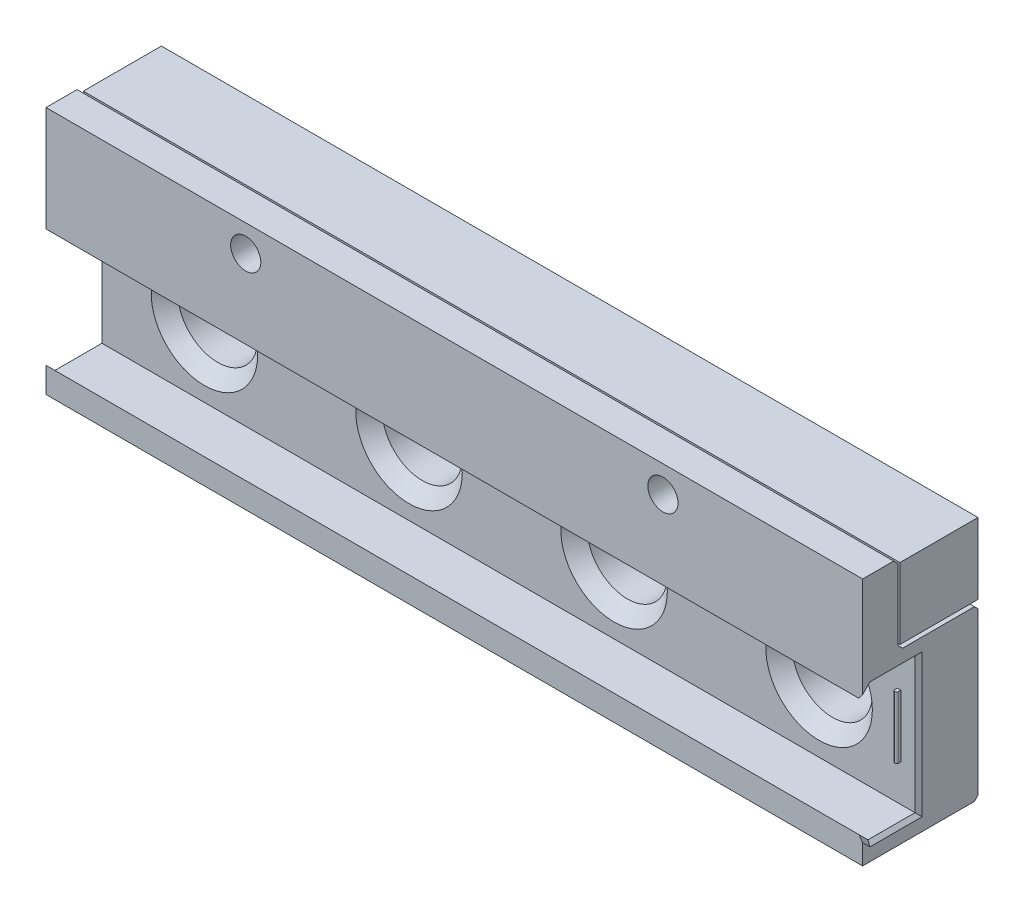
SolidWorks part; units mm, degrees
ref_plane "Front Plane" through (0, 0, 0) normal (0, 0, 1) x (1, 0, 0)
ref_plane "Top Plane" through (0, 0, 0) normal (0, 1, 0) x (1, 0, 0)
ref_plane "Right Plane" through (0, 0, 0) normal (1, 0, 0) x (0, 0, -1)
sketch "Sketch1" plane through (0, 0, 0) normal (0, 0, 1) x (1, 0, 0)
  line L1 (-61.1072, 25.5521) -> (30.8928, 25.5521)
  line L2 (-61.1072, 25.5521) -> (-61.1072, 6.5521)
  line L3 (-61.1072, 6.5521) -> (30.8928, 6.5521)
  line L4 (30.8928, 25.5521) -> (30.8928, 6.5521)
  dimension "D1" = 92
  dimension "D2" = 19
extrude "Boss-Extrude1" add sketch "Sketch1" along normal blind 13
sketch "Sketch2" plane through (0, 0, 13) normal (0, 0, 1) x (1, 0, 0)
  line L0 (-61.1072, 25.5521) -> (-61.1072, 6.5521) construction
  line L1 (-61.1072, 6.5521) -> (30.8928, 6.5521) construction
  circle A0 centre (-49.5572, 16.0521) radius 4.5
  dimension "D1" = 9
  dimension "D2" = 11.55
  dimension "D3" = 9.5
extrude "Cut-Extrude1" cut sketch "Sketch2" against normal through all
sketch "Sketch4" plane through (0, 0, 13) normal (0, 0, 1) x (1, 0, 0)
  line L0 (-61.1072, 6.5521) -> (30.8928, 6.5521) construction
  circle A0 centre (-26.5072, 16.0521) radius 4.5
  circle A1 centre (-49.5572, 16.0521) radius 4.5 construction
  dimension "D2" = 9
  dimension "D1" = 23.05
  dimension "D3" = 9.5
extrude "Cut-Extrude2" cut sketch "Sketch4" against normal through all
sketch "Sketch5" plane through (0, 0, 13) normal (0, 0, 1) x (1, 0, 0)
  line L0 (-61.1072, 6.5521) -> (30.8928, 6.5521) construction
  circle A0 centre (-3.4072, 16.0521) radius 4.5
  circle A1 centre (-26.5072, 16.0521) radius 4.5 construction
  dimension "D2" = 9
  dimension "D1" = 23.1
  dimension "D3" = 9.5
extrude "Cut-Extrude3" cut sketch "Sketch5" against normal through all
sketch "Sketch6" plane through (0, 0, 13) normal (0, 0, 1) x (1, 0, 0)
  line L0 (-61.1072, 6.5521) -> (30.8928, 6.5521) construction
  circle A0 centre (19.6928, 16.0521) radius 4.5
  circle A1 centre (-3.4072, 16.0521) radius 4.5 construction
  dimension "D3" = 9
  dimension "D1" = 23.1
  dimension "D2" = 9.5
extrude "Cut-Extrude4" cut sketch "Sketch6" against normal through all
sketch "Sketch7" plane through (0, 0, 13) normal (0, 0, 1) x (1, 0, 0)
  line L0 (-61.1072, 25.5521) -> (-61.1072, 6.5521) construction
  line L1 (-61.1072, 23.7021) -> (30.8928, 23.7021)
  line L2 (-61.1072, 23.7021) -> (-61.1072, 8.4021)
  line L3 (-61.1072, 8.4021) -> (30.8928, 8.4021)
  line L4 (30.8928, 23.7021) -> (30.8928, 8.4021)
  line L5 (30.8928, 6.5521) -> (30.8928, 25.5521) construction
  line L6 (30.8928, 25.5521) -> (-61.1072, 25.5521) construction
  line L7 (-61.1072, 6.5521) -> (30.8928, 6.5521) construction
  dimension "D1" = 1.85
  dimension "D2" = 1.85
extrude "Cut-Extrude5" cut sketch "Sketch7" against normal blind 6.3
sketch "Sketch11" plane through (0, 25.5521, 0) normal (0, 1, 0) x (1, 0, 0)
  line L0 (30.8928, -13) -> (30.8928, 0) construction
  line L1 (-61.1072, -13) -> (30.8928, -13)
  line L2 (-61.1072, -13) -> (-61.1072, -9)
  line L3 (-61.1072, -9) -> (30.8928, -9)
  line L4 (30.8928, -13) -> (30.8928, -9)
  dimension "D1" = 4
extrude "Boss-Extrude4" add sketch "Sketch11" along normal blind 9
sketch "Sketch12" plane through (0, 0, 13) normal (0, 0, 1) x (1, 0, 0)
  line L0 (-61.1072, 34.5521) -> (30.8928, 34.5521) construction
  line L1 (-61.1072, 34.5521) -> (-61.1072, 23.7021) construction
  circle A0 centre (-38.6072, 31.5521) radius 1.7
  dimension "D1" = 3.4
  dimension "D2" = 3
  dimension "D3" = 22.5
extrude "Cut-Extrude6" cut sketch "Sketch12" against normal through all
sketch "Sketch13" plane through (0, 0, 13) normal (0, 0, 1) x (1, 0, 0)
  line L0 (-61.1072, 34.5521) -> (30.8928, 34.5521) construction
  line L1 (30.8928, 23.7021) -> (30.8928, 34.5521) construction
  circle A0 centre (8.3928, 31.5521) radius 1.7
  dimension "D1" = 3.4
  dimension "D2" = 3
  dimension "D3" = 22.5
extrude "Cut-Extrude7" cut sketch "Sketch13" against normal through all
chamfer "Chamfer1" distance 0.4 angle 45 2 edges at (-15.1072, 25.5521, 0) (-15.1072, 6.5521, 0)
chamfer "Chamfer2" distance 0.5 angle 45 2 edges at (-36.9072, 31.5521, 9) (10.0928, 31.5521, 9)
chamfer "Chamfer3" distance 0.5 angle 45 1 edges at (-15.1072, 25.5521, 9)
chamfer "Chamfer4" distance 0.5 angle 45 1 edges at (-15.1072, 34.5521, 9)
sketch "Sketch14" plane through (0, 0, 0) normal (0, 0, -1) x (-1, 0, 0)
  line L1 (-30.8928, 34.0521) -> (61.1072, 34.0521)
  line L2 (-30.8928, 34.0521) -> (-30.8928, 26.0521)
  line L3 (-30.8928, 26.0521) -> (61.1072, 26.0521)
  line L4 (61.1072, 34.0521) -> (61.1072, 26.0521)
extrude "Boss-Extrude5" add sketch "Sketch14" against normal blind 8.8 separate body
chamfer "Chamfer5" distance 1.5 angle 45 4 edges at (24.1928, 16.0521, 6.7) (1.0928, 16.0521, 6.7) (-22.0072, 16.0521, 6.7) (-45.0572, 16.0521, 6.7)
sketch "Sketch19" plane through (30.8928, 0, 0) normal (1, 0, 0) x (0, 0, -1)
  line L0 (-13, 23.7021) -> (-12, 23.7021)
  line L1 (-6.7, 23.7021) -> (-13, 23.7021) construction
  line L2 (-12, 23.7021) -> (-13, 22.7021)
  line L3 (-13, 22.7021) -> (-13, 23.7021)
  line L4 (-13, 8.4021) -> (-12, 8.4021)
  line L5 (-6.7, 8.4021) -> (-13, 8.4021) construction
  line L6 (-12, 8.4021) -> (-13, 9.4021)
  line L7 (-13, 9.4021) -> (-13, 8.4021)
  dimension "D1" = 1
  dimension "D2" = 1
  dimension "D3" = 1
extrude "Boss-Extrude8" add sketch "Sketch19" against normal up to surface (92 mm away) up to face at (-61.1072, 20.695, 7.3)
sketch "Sketch20" plane through (0, 0, 6.7) normal (0, 0, 1) x (1, 0, 0)
  line L1 (28.4928, 19.5521) -> (28.8928, 19.5521)
  line L2 (28.4928, 19.5521) -> (28.4928, 12.5521)
  line L3 (28.4928, 12.5521) -> (28.8928, 12.5521)
  line L4 (28.8928, 19.5521) -> (28.8928, 12.5521)
  line L5 (30.8928, 23.7021) -> (-61.1072, 23.7021) construction
  line L6 (30.8928, 8.4021) -> (30.8928, 23.7021) construction
  dimension "D1" = 0.4
  dimension "D2" = 7
  dimension "D3" = 2
  dimension "D4" = 4.15
chamfer "Chamfer6" distance 0.4 angle 45 5 edges at (30.8928, 23.2021, 12.5) (30.8928, 23.7021, 9.35) (30.8928, 16.0521, 6.7) (30.8928, 8.4021, 9.35) (30.8928, 8.9021, 12.5)
extrude "Boss-Extrude9" add sketch "Sketch20" along normal blind 0.75
fillet "Fillet1" radius 0.5 1 edges at (28.4928, 16.0521, 7.45)
fillet "Fillet2" radius 0.2 1 edges at (28.8928, 16.0521, 7.45)
sketch "Sketch25" plane through (0, 0, 8.8) normal (0, 0, 1) x (1, 0, 0)
  line L0 (-61.1072, 26.0521) -> (-61.1072, 34.0521) construction
  line L1 (-60.1072, 33.0521) -> (29.8928, 33.0521)
  line L2 (-60.1072, 33.0521) -> (-60.1072, 27.0521)
  line L3 (-60.1072, 27.0521) -> (29.8928, 27.0521)
  line L4 (29.8928, 33.0521) -> (29.8928, 27.0521)
  line L5 (-61.1072, 34.0521) -> (30.8928, 34.0521) construction
  line L6 (30.8928, 26.0521) -> (-61.1072, 26.0521) construction
  line L7 (30.8928, 34.0521) -> (30.8928, 26.0521) construction
  dimension "D1" = 1
  dimension "D2" = 1
  dimension "D3" = 1
  dimension "D4" = 1
extrude "Cut-Extrude10" cut sketch "Sketch25" against normal blind 1
sketch "Sketch26" plane through (0, 0, 0) normal (0, 0, -1) x (-1, 0, 0)
  line L0 (-30.8928, 34.0521) -> (-30.8928, 26.0521) construction
  line L1 (-29.8928, 33.0521) -> (60.1072, 33.0521)
  line L2 (-29.8928, 33.0521) -> (-29.8928, 27.0521)
  line L3 (-29.8928, 27.0521) -> (60.1072, 27.0521)
  line L4 (60.1072, 33.0521) -> (60.1072, 27.0521)
  line L5 (61.1072, 34.0521) -> (-30.8928, 34.0521) construction
  line L6 (-30.8928, 26.0521) -> (61.1072, 26.0521) construction
  line L7 (61.1072, 26.0521) -> (61.1072, 34.0521) construction
  dimension "D1" = 1
  dimension "D2" = 1
  dimension "D3" = 1
  dimension "D4" = 1
extrude "Cut-Extrude11" cut sketch "Sketch26" against normal blind 6.9
sketch "Sketch28" plane through (0, 0, 8.8) normal (0, 0, 1) x (1, 0, 0)
  line L0 (-60.1072, 33.0521) -> (-55.906, 27.0521)
  line L1 (-60.1072, 27.0521) -> (29.8928, 27.0521) construction
  line L2 (-55.906, 27.0521) -> (-54.906, 27.0521)
  line L3 (-54.906, 27.0521) -> (-59.1072, 33.0521)
  line L4 (29.8928, 33.0521) -> (-60.1072, 33.0521) construction
  line L5 (-59.1072, 33.0521) -> (-60.1072, 33.0521)
  line L6 (-61.1072, 26.0521) -> (-61.1072, 34.0521) construction
  dimension "D1" = 1
  dimension "D2" = 35
  dimension "D3" = 1
extrude "Boss-Extrude13" add sketch "Sketch28" against normal blind 1
sketch "Sketch29" plane through (0, 0, 8.8) normal (0, 0, 1) x (1, 0, 0)
  line L0 (-60.1072, 27.0521) -> (-59.1072, 27.0521)
  line L1 (-60.1072, 27.0521) -> (-55.906, 27.0521) construction
  line L2 (-59.1072, 27.0521) -> (-54.906, 33.0521)
  line L3 (29.8928, 33.0521) -> (-59.1072, 33.0521) construction
  line L4 (-54.906, 33.0521) -> (-55.906, 33.0521)
  line L5 (29.8928, 33.0521) -> (-59.1072, 33.0521) construction
  line L6 (-55.906, 33.0521) -> (-60.1072, 27.0521)
  line L7 (-61.1072, 26.0521) -> (-61.1072, 34.0521) construction
  line L8 (-60.1072, 33.0521) -> (-60.1072, 27.0521) construction
  dimension "D1" = 1
  dimension "D2" = 1
  dimension "D3" = 1
  dimension "D4" = 35
extrude "Boss-Extrude14" add sketch "Sketch29" against normal blind 1
pattern_linear "LPattern4" count 22 spacing 4.04 along (1, 0, 0) of "Boss-Extrude13", "Boss-Extrude14"
sketch "Sketch30" plane through (0, 0, 0) normal (0, 0, -1) x (-1, 0, 0)
  line L0 (60.1072, 33.0521) -> (-29.8928, 33.0521) construction
  line L1 (-26.8928, 33.0521) -> (-25.8928, 33.0521)
  line L2 (-26.8928, 33.0521) -> (-26.8928, 27.0521)
  line L3 (-26.8928, 27.0521) -> (-25.8928, 27.0521)
  line L4 (-25.8928, 33.0521) -> (-25.8928, 27.0521)
  line L5 (-29.8928, 27.0521) -> (60.1072, 27.0521) construction
  line L6 (-29.8928, 33.0521) -> (-29.8928, 27.0521) construction
  dimension "D1" = 1
  dimension "D2" = 3
extrude "Boss-Extrude15" add sketch "Sketch30" against normal up to surface (6.9 mm away) up to face at (-15.1072, 30.0521, 6.9)
pattern_linear "LPattern5" count 22 spacing 4 along (-1, 0, 0) of "Boss-Extrude15"
sketch "Sketch31" plane through (0, 0, 8.8) normal (0, 0, 1) x (1, 0, 0)
  circle A0 centre (8.3928, 31.5521) radius 2.5
  circle A1 centre (-38.6072, 31.5521) radius 2.5
extrude "Boss-Extrude16" add sketch "Sketch31" against normal up to surface (1 mm away) up to face at (1.0734, 30.0521, 7.8)
sketch "Sketch32" plane through (0, 0, 8.8) normal (0, 0, 1) x (1, 0, 0)
  circle A0 centre (-38.6072, 31.5521) radius 1.5
  circle A1 centre (8.3928, 31.5521) radius 1.5
  dimension "D1" = 3
  dimension "D2" = 3
extrude "Cut-Extrude12" cut sketch "Sketch32" against normal blind 1
